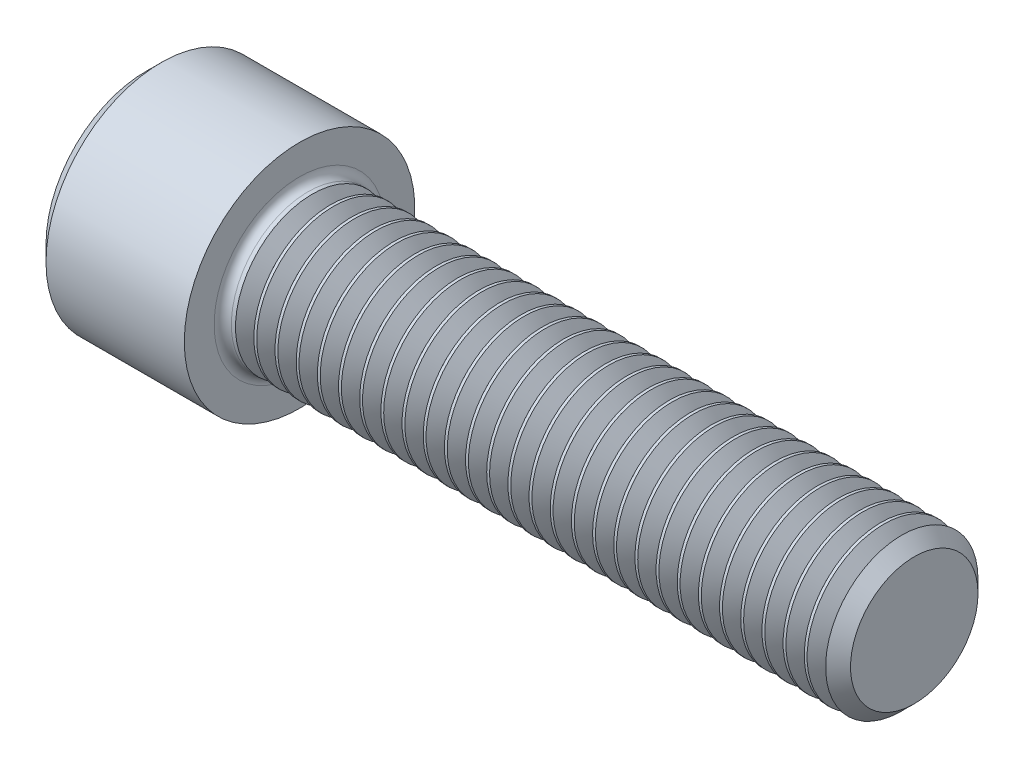
SolidWorks part; units mm, degrees
material "Chrome Stainless Steel"
ref_plane "Front Plane" through (0, 0, 0) normal (0, 0, 1) x (1, 0, 0)
ref_plane "Top Plane" through (0, 0, 0) normal (0, 1, 0) x (1, 0, 0)
ref_plane "Right Plane" through (0, 0, 0) normal (1, 0, 0) x (0, 0, -1)
ref_plane "Plane1" through (0, 0, 0) normal (0, 0, -1) x (-1, 0, 0)
sketch "Sketch1" plane through (0, 0, 0) normal (0, 0, -1) x (-1, 0, 0)
  line L0 (-6.35, 4.7625) -> (-6.35, 0)
  line L1 (-6.35, 0) -> (0, 0)
  line L2 (0, 0) -> (0, 4.7625)
  line L3 (0, 4.7625) -> (-6.35, 4.7625)
  line L4 (-6.35, 0) -> (0, 0) construction
revolve "Revolve1" add sketch "Sketch1" angle 360 about L4 reverse direction yes
sketch "Sketch2" plane through (6.35, 0, 0) normal (1, 0, 0) x (0, 0, -1)
  circle A0 centre (0, 0) radius 3.175
extrude "Boss-Extrude1" add sketch "Sketch2" along normal blind 0.528
sketch "Sketch3" plane through (6.878, 0, 0) normal (1, 0, 0) x (0, 0, -1)
  circle A0 centre (0, 0) radius 3.175
extrude "Boss-Extrude2" add sketch "Sketch3" along normal blind 0.3788 draft 55
sketch "Sketch4" plane through (7.2568, 0, 0) normal (1, 0, 0) x (0, 0, -1)
  circle A0 centre (0, 0) radius 2.634
extrude "Boss-Extrude3" add sketch "Sketch4" along normal blind 0.3788 draft 55 draft outward yes
sketch "Sketch5" plane through (7.6356, 0, 0) normal (1, 0, 0) x (0, 0, -1)
  circle A0 centre (0, 0) radius 3.175
extrude "Boss-Extrude4" add sketch "Sketch5" along normal blind 0.1171
sketch "Sketch6" plane through (7.7527, 0, 0) normal (1, 0, 0) x (0, 0, -1)
  circle A0 centre (0, 0) radius 3.175
extrude "Boss-Extrude5" add sketch "Sketch6" along normal blind 0.3788 draft 55
sketch "Sketch7" plane through (8.1315, 0, 0) normal (1, 0, 0) x (0, 0, -1)
  circle A0 centre (0, 0) radius 2.634
extrude "Boss-Extrude6" add sketch "Sketch7" along normal blind 0.3788 draft 55 draft outward yes
sketch "Sketch8" plane through (8.5104, 0, 0) normal (1, 0, 0) x (0, 0, -1)
  circle A0 centre (0, 0) radius 3.175
extrude "Boss-Extrude7" add sketch "Sketch8" along normal blind 0.1171
sketch "Sketch9" plane through (8.6275, 0, 0) normal (1, 0, 0) x (0, 0, -1)
  circle A0 centre (0, 0) radius 3.175
extrude "Boss-Extrude8" add sketch "Sketch9" along normal blind 0.3788 draft 55
sketch "Sketch10" plane through (9.0063, 0, 0) normal (1, 0, 0) x (0, 0, -1)
  circle A0 centre (0, 0) radius 2.634
extrude "Boss-Extrude9" add sketch "Sketch10" along normal blind 0.3788 draft 55 draft outward yes
sketch "Sketch11" plane through (9.3851, 0, 0) normal (1, 0, 0) x (0, 0, -1)
  circle A0 centre (0, 0) radius 3.175
extrude "Boss-Extrude10" add sketch "Sketch11" along normal blind 0.1171
sketch "Sketch12" plane through (9.5022, 0, 0) normal (1, 0, 0) x (0, 0, -1)
  circle A0 centre (0, 0) radius 3.175
extrude "Boss-Extrude11" add sketch "Sketch12" along normal blind 0.3788 draft 55
sketch "Sketch13" plane through (9.8811, 0, 0) normal (1, 0, 0) x (0, 0, -1)
  circle A0 centre (0, 0) radius 2.634
extrude "Boss-Extrude12" add sketch "Sketch13" along normal blind 0.3788 draft 55 draft outward yes
sketch "Sketch14" plane through (10.2599, 0, 0) normal (1, 0, 0) x (0, 0, -1)
  circle A0 centre (0, 0) radius 3.175
extrude "Boss-Extrude13" add sketch "Sketch14" along normal blind 0.1171
sketch "Sketch15" plane through (10.377, 0, 0) normal (1, 0, 0) x (0, 0, -1)
  circle A0 centre (0, 0) radius 3.175
extrude "Boss-Extrude14" add sketch "Sketch15" along normal blind 0.3788 draft 55
sketch "Sketch16" plane through (10.7558, 0, 0) normal (1, 0, 0) x (0, 0, -1)
  circle A0 centre (0, 0) radius 2.634
extrude "Boss-Extrude15" add sketch "Sketch16" along normal blind 0.3788 draft 55 draft outward yes
sketch "Sketch17" plane through (11.1346, 0, 0) normal (1, 0, 0) x (0, 0, -1)
  circle A0 centre (0, 0) radius 3.175
extrude "Boss-Extrude16" add sketch "Sketch17" along normal blind 0.1171
sketch "Sketch18" plane through (11.2517, 0, 0) normal (1, 0, 0) x (0, 0, -1)
  circle A0 centre (0, 0) radius 3.175
extrude "Boss-Extrude17" add sketch "Sketch18" along normal blind 0.3788 draft 55
sketch "Sketch19" plane through (11.6306, 0, 0) normal (1, 0, 0) x (0, 0, -1)
  circle A0 centre (0, 0) radius 2.634
extrude "Boss-Extrude18" add sketch "Sketch19" along normal blind 0.3788 draft 55 draft outward yes
sketch "Sketch20" plane through (12.0094, 0, 0) normal (1, 0, 0) x (0, 0, -1)
  circle A0 centre (0, 0) radius 3.175
extrude "Boss-Extrude19" add sketch "Sketch20" along normal blind 0.1171
sketch "Sketch21" plane through (12.1265, 0, 0) normal (1, 0, 0) x (0, 0, -1)
  circle A0 centre (0, 0) radius 3.175
extrude "Boss-Extrude20" add sketch "Sketch21" along normal blind 0.3788 draft 55
sketch "Sketch22" plane through (12.5053, 0, 0) normal (1, 0, 0) x (0, 0, -1)
  circle A0 centre (0, 0) radius 2.634
extrude "Boss-Extrude21" add sketch "Sketch22" along normal blind 0.3788 draft 55 draft outward yes
sketch "Sketch23" plane through (12.8842, 0, 0) normal (1, 0, 0) x (0, 0, -1)
  circle A0 centre (0, 0) radius 3.175
extrude "Boss-Extrude22" add sketch "Sketch23" along normal blind 0.1171
sketch "Sketch24" plane through (13.0013, 0, 0) normal (1, 0, 0) x (0, 0, -1)
  circle A0 centre (0, 0) radius 3.175
extrude "Boss-Extrude23" add sketch "Sketch24" along normal blind 0.3788 draft 55
sketch "Sketch25" plane through (13.3801, 0, 0) normal (1, 0, 0) x (0, 0, -1)
  circle A0 centre (0, 0) radius 2.634
extrude "Boss-Extrude24" add sketch "Sketch25" along normal blind 0.3788 draft 55 draft outward yes
sketch "Sketch26" plane through (13.7589, 0, 0) normal (1, 0, 0) x (0, 0, -1)
  circle A0 centre (0, 0) radius 3.175
extrude "Boss-Extrude25" add sketch "Sketch26" along normal blind 0.1171
sketch "Sketch27" plane through (13.876, 0, 0) normal (1, 0, 0) x (0, 0, -1)
  circle A0 centre (0, 0) radius 3.175
extrude "Boss-Extrude26" add sketch "Sketch27" along normal blind 0.3788 draft 55
sketch "Sketch28" plane through (14.2548, 0, 0) normal (1, 0, 0) x (0, 0, -1)
  circle A0 centre (0, 0) radius 2.634
extrude "Boss-Extrude27" add sketch "Sketch28" along normal blind 0.3788 draft 55 draft outward yes
sketch "Sketch29" plane through (14.6337, 0, 0) normal (1, 0, 0) x (0, 0, -1)
  circle A0 centre (0, 0) radius 3.175
extrude "Boss-Extrude28" add sketch "Sketch29" along normal blind 0.1171
sketch "Sketch30" plane through (14.7508, 0, 0) normal (1, 0, 0) x (0, 0, -1)
  circle A0 centre (0, 0) radius 3.175
extrude "Boss-Extrude29" add sketch "Sketch30" along normal blind 0.3788 draft 55
sketch "Sketch31" plane through (15.1296, 0, 0) normal (1, 0, 0) x (0, 0, -1)
  circle A0 centre (0, 0) radius 2.634
extrude "Boss-Extrude30" add sketch "Sketch31" along normal blind 0.3788 draft 55 draft outward yes
sketch "Sketch32" plane through (15.5084, 0, 0) normal (1, 0, 0) x (0, 0, -1)
  circle A0 centre (0, 0) radius 3.175
extrude "Boss-Extrude31" add sketch "Sketch32" along normal blind 0.1171
sketch "Sketch33" plane through (15.6255, 0, 0) normal (1, 0, 0) x (0, 0, -1)
  circle A0 centre (0, 0) radius 3.175
extrude "Boss-Extrude32" add sketch "Sketch33" along normal blind 0.3788 draft 55
sketch "Sketch34" plane through (16.0044, 0, 0) normal (1, 0, 0) x (0, 0, -1)
  circle A0 centre (0, 0) radius 2.634
extrude "Boss-Extrude33" add sketch "Sketch34" along normal blind 0.3788 draft 55 draft outward yes
sketch "Sketch35" plane through (16.3832, 0, 0) normal (1, 0, 0) x (0, 0, -1)
  circle A0 centre (0, 0) radius 3.175
extrude "Boss-Extrude34" add sketch "Sketch35" along normal blind 0.1171
sketch "Sketch36" plane through (16.5003, 0, 0) normal (1, 0, 0) x (0, 0, -1)
  circle A0 centre (0, 0) radius 3.175
extrude "Boss-Extrude35" add sketch "Sketch36" along normal blind 0.3788 draft 55
sketch "Sketch37" plane through (16.8791, 0, 0) normal (1, 0, 0) x (0, 0, -1)
  circle A0 centre (0, 0) radius 2.634
extrude "Boss-Extrude36" add sketch "Sketch37" along normal blind 0.3788 draft 55 draft outward yes
sketch "Sketch38" plane through (17.2579, 0, 0) normal (1, 0, 0) x (0, 0, -1)
  circle A0 centre (0, 0) radius 3.175
extrude "Boss-Extrude37" add sketch "Sketch38" along normal blind 0.1171
sketch "Sketch39" plane through (17.375, 0, 0) normal (1, 0, 0) x (0, 0, -1)
  circle A0 centre (0, 0) radius 3.175
extrude "Boss-Extrude38" add sketch "Sketch39" along normal blind 0.3788 draft 55
sketch "Sketch40" plane through (17.7539, 0, 0) normal (1, 0, 0) x (0, 0, -1)
  circle A0 centre (0, 0) radius 2.634
extrude "Boss-Extrude39" add sketch "Sketch40" along normal blind 0.3788 draft 55 draft outward yes
sketch "Sketch41" plane through (18.1327, 0, 0) normal (1, 0, 0) x (0, 0, -1)
  circle A0 centre (0, 0) radius 3.175
extrude "Boss-Extrude40" add sketch "Sketch41" along normal blind 0.1171
sketch "Sketch42" plane through (18.2498, 0, 0) normal (1, 0, 0) x (0, 0, -1)
  circle A0 centre (0, 0) radius 3.175
extrude "Boss-Extrude41" add sketch "Sketch42" along normal blind 0.3788 draft 55
sketch "Sketch43" plane through (18.6286, 0, 0) normal (1, 0, 0) x (0, 0, -1)
  circle A0 centre (0, 0) radius 2.634
extrude "Boss-Extrude42" add sketch "Sketch43" along normal blind 0.3788 draft 55 draft outward yes
sketch "Sketch44" plane through (19.0075, 0, 0) normal (1, 0, 0) x (0, 0, -1)
  circle A0 centre (0, 0) radius 3.175
extrude "Boss-Extrude43" add sketch "Sketch44" along normal blind 0.1171
sketch "Sketch45" plane through (19.1246, 0, 0) normal (1, 0, 0) x (0, 0, -1)
  circle A0 centre (0, 0) radius 3.175
extrude "Boss-Extrude44" add sketch "Sketch45" along normal blind 0.3788 draft 55
sketch "Sketch46" plane through (19.5034, 0, 0) normal (1, 0, 0) x (0, 0, -1)
  circle A0 centre (0, 0) radius 2.634
extrude "Boss-Extrude45" add sketch "Sketch46" along normal blind 0.3788 draft 55 draft outward yes
sketch "Sketch47" plane through (19.8822, 0, 0) normal (1, 0, 0) x (0, 0, -1)
  circle A0 centre (0, 0) radius 3.175
extrude "Boss-Extrude46" add sketch "Sketch47" along normal blind 0.1171
sketch "Sketch48" plane through (19.9993, 0, 0) normal (1, 0, 0) x (0, 0, -1)
  circle A0 centre (0, 0) radius 3.175
extrude "Boss-Extrude47" add sketch "Sketch48" along normal blind 0.3788 draft 55
sketch "Sketch49" plane through (20.3781, 0, 0) normal (1, 0, 0) x (0, 0, -1)
  circle A0 centre (0, 0) radius 2.634
extrude "Boss-Extrude48" add sketch "Sketch49" along normal blind 0.3788 draft 55 draft outward yes
sketch "Sketch50" plane through (20.757, 0, 0) normal (1, 0, 0) x (0, 0, -1)
  circle A0 centre (0, 0) radius 3.175
extrude "Boss-Extrude49" add sketch "Sketch50" along normal blind 0.1171
sketch "Sketch51" plane through (20.8741, 0, 0) normal (1, 0, 0) x (0, 0, -1)
  circle A0 centre (0, 0) radius 3.175
extrude "Boss-Extrude50" add sketch "Sketch51" along normal blind 0.3788 draft 55
sketch "Sketch52" plane through (21.2529, 0, 0) normal (1, 0, 0) x (0, 0, -1)
  circle A0 centre (0, 0) radius 2.634
extrude "Boss-Extrude51" add sketch "Sketch52" along normal blind 0.3788 draft 55 draft outward yes
sketch "Sketch53" plane through (21.6317, 0, 0) normal (1, 0, 0) x (0, 0, -1)
  circle A0 centre (0, 0) radius 3.175
extrude "Boss-Extrude52" add sketch "Sketch53" along normal blind 0.1171
sketch "Sketch54" plane through (21.7488, 0, 0) normal (1, 0, 0) x (0, 0, -1)
  circle A0 centre (0, 0) radius 3.175
extrude "Boss-Extrude53" add sketch "Sketch54" along normal blind 0.3788 draft 55
sketch "Sketch55" plane through (22.1277, 0, 0) normal (1, 0, 0) x (0, 0, -1)
  circle A0 centre (0, 0) radius 2.634
extrude "Boss-Extrude54" add sketch "Sketch55" along normal blind 0.3788 draft 55 draft outward yes
sketch "Sketch56" plane through (22.5065, 0, 0) normal (1, 0, 0) x (0, 0, -1)
  circle A0 centre (0, 0) radius 3.175
extrude "Boss-Extrude55" add sketch "Sketch56" along normal blind 0.1171
sketch "Sketch57" plane through (22.6236, 0, 0) normal (1, 0, 0) x (0, 0, -1)
  circle A0 centre (0, 0) radius 3.175
extrude "Boss-Extrude56" add sketch "Sketch57" along normal blind 0.3788 draft 55
sketch "Sketch58" plane through (23.0024, 0, 0) normal (1, 0, 0) x (0, 0, -1)
  circle A0 centre (0, 0) radius 2.634
extrude "Boss-Extrude57" add sketch "Sketch58" along normal blind 0.3788 draft 55 draft outward yes
sketch "Sketch59" plane through (23.3812, 0, 0) normal (1, 0, 0) x (0, 0, -1)
  circle A0 centre (0, 0) radius 3.175
extrude "Boss-Extrude58" add sketch "Sketch59" along normal blind 0.1171
sketch "Sketch60" plane through (23.4984, 0, 0) normal (1, 0, 0) x (0, 0, -1)
  circle A0 centre (0, 0) radius 3.175
extrude "Boss-Extrude59" add sketch "Sketch60" along normal blind 0.3788 draft 55
sketch "Sketch61" plane through (23.8772, 0, 0) normal (1, 0, 0) x (0, 0, -1)
  circle A0 centre (0, 0) radius 2.634
extrude "Boss-Extrude60" add sketch "Sketch61" along normal blind 0.3788 draft 55 draft outward yes
sketch "Sketch62" plane through (24.256, 0, 0) normal (1, 0, 0) x (0, 0, -1)
  circle A0 centre (0, 0) radius 3.175
extrude "Boss-Extrude61" add sketch "Sketch62" along normal blind 0.1171
sketch "Sketch63" plane through (24.3731, 0, 0) normal (1, 0, 0) x (0, 0, -1)
  circle A0 centre (0, 0) radius 3.175
extrude "Boss-Extrude62" add sketch "Sketch63" along normal blind 0.3788 draft 55
sketch "Sketch64" plane through (24.7519, 0, 0) normal (1, 0, 0) x (0, 0, -1)
  circle A0 centre (0, 0) radius 2.634
extrude "Boss-Extrude63" add sketch "Sketch64" along normal blind 0.3788 draft 55 draft outward yes
sketch "Sketch65" plane through (25.1308, 0, 0) normal (1, 0, 0) x (0, 0, -1)
  circle A0 centre (0, 0) radius 3.175
extrude "Boss-Extrude64" add sketch "Sketch65" along normal blind 0.1171
sketch "Sketch66" plane through (25.2479, 0, 0) normal (1, 0, 0) x (0, 0, -1)
  circle A0 centre (0, 0) radius 3.175
extrude "Boss-Extrude65" add sketch "Sketch66" along normal blind 0.3788 draft 55
sketch "Sketch67" plane through (25.6267, 0, 0) normal (1, 0, 0) x (0, 0, -1)
  circle A0 centre (0, 0) radius 2.634
extrude "Boss-Extrude66" add sketch "Sketch67" along normal blind 0.3788 draft 55 draft outward yes
sketch "Sketch68" plane through (26.0055, 0, 0) normal (1, 0, 0) x (0, 0, -1)
  circle A0 centre (0, 0) radius 3.175
extrude "Boss-Extrude67" add sketch "Sketch68" along normal blind 0.1171
sketch "Sketch69" plane through (26.1226, 0, 0) normal (1, 0, 0) x (0, 0, -1)
  circle A0 centre (0, 0) radius 3.175
extrude "Boss-Extrude68" add sketch "Sketch69" along normal blind 0.3788 draft 55
sketch "Sketch70" plane through (26.5015, 0, 0) normal (1, 0, 0) x (0, 0, -1)
  circle A0 centre (0, 0) radius 2.634
extrude "Boss-Extrude69" add sketch "Sketch70" along normal blind 0.3788 draft 55 draft outward yes
sketch "Sketch71" plane through (26.8803, 0, 0) normal (1, 0, 0) x (0, 0, -1)
  circle A0 centre (0, 0) radius 3.175
extrude "Boss-Extrude70" add sketch "Sketch71" along normal blind 0.1171
sketch "Sketch72" plane through (26.9974, 0, 0) normal (1, 0, 0) x (0, 0, -1)
  circle A0 centre (0, 0) radius 3.175
extrude "Boss-Extrude71" add sketch "Sketch72" along normal blind 0.3788 draft 55
sketch "Sketch73" plane through (27.3762, 0, 0) normal (1, 0, 0) x (0, 0, -1)
  circle A0 centre (0, 0) radius 2.634
extrude "Boss-Extrude72" add sketch "Sketch73" along normal blind 0.3788 draft 55 draft outward yes
sketch "Sketch74" plane through (27.755, 0, 0) normal (1, 0, 0) x (0, 0, -1)
  circle A0 centre (0, 0) radius 3.175
extrude "Boss-Extrude73" add sketch "Sketch74" along normal blind 0.1171
sketch "Sketch75" plane through (27.8721, 0, 0) normal (1, 0, 0) x (0, 0, -1)
  circle A0 centre (0, 0) radius 3.175
extrude "Boss-Extrude74" add sketch "Sketch75" along normal blind 0.3788 draft 55
sketch "Sketch76" plane through (28.251, 0, 0) normal (1, 0, 0) x (0, 0, -1)
  circle A0 centre (0, 0) radius 2.634
extrude "Boss-Extrude75" add sketch "Sketch76" along normal blind 0.3788 draft 55 draft outward yes
sketch "Sketch77" plane through (28.6298, 0, 0) normal (1, 0, 0) x (0, 0, -1)
  circle A0 centre (0, 0) radius 3.175
extrude "Boss-Extrude76" add sketch "Sketch77" along normal blind 0.1171
sketch "Sketch78" plane through (28.7469, 0, 0) normal (1, 0, 0) x (0, 0, -1)
  circle A0 centre (0, 0) radius 3.175
extrude "Boss-Extrude77" add sketch "Sketch78" along normal blind 0.3788 draft 55
sketch "Sketch79" plane through (29.1257, 0, 0) normal (1, 0, 0) x (0, 0, -1)
  circle A0 centre (0, 0) radius 2.634
extrude "Boss-Extrude78" add sketch "Sketch79" along normal blind 0.3788 draft 55 draft outward yes
sketch "Sketch80" plane through (29.5046, 0, 0) normal (1, 0, 0) x (0, 0, -1)
  circle A0 centre (0, 0) radius 3.175
extrude "Boss-Extrude79" add sketch "Sketch80" along normal blind 0.1171
sketch "Sketch81" plane through (29.6217, 0, 0) normal (1, 0, 0) x (0, 0, -1)
  circle A0 centre (0, 0) radius 3.175
extrude "Boss-Extrude80" add sketch "Sketch81" along normal blind 0.3788 draft 55
sketch "Sketch82" plane through (30.0005, 0, 0) normal (1, 0, 0) x (0, 0, -1)
  circle A0 centre (0, 0) radius 2.634
extrude "Boss-Extrude81" add sketch "Sketch82" along normal blind 0.3788 draft 55 draft outward yes
sketch "Sketch83" plane through (30.3793, 0, 0) normal (1, 0, 0) x (0, 0, -1)
  circle A0 centre (0, 0) radius 3.175
extrude "Boss-Extrude82" add sketch "Sketch83" along normal blind 0.1171
sketch "Sketch84" plane through (30.4964, 0, 0) normal (1, 0, 0) x (0, 0, -1)
  circle A0 centre (0, 0) radius 3.175
extrude "Boss-Extrude83" add sketch "Sketch84" along normal blind 0.3788 draft 55
sketch "Sketch85" plane through (30.8752, 0, 0) normal (1, 0, 0) x (0, 0, -1)
  circle A0 centre (0, 0) radius 2.634
extrude "Boss-Extrude84" add sketch "Sketch85" along normal blind 0.3603 draft 55 draft outward yes
sketch "Sketch86" plane through (31.2355, 0, 0) normal (1, 0, 0) x (0, 0, -1)
  circle A0 centre (0, 0) radius 3.1485
extrude "Boss-Extrude85" add sketch "Sketch86" along normal blind 0.5145 draft 45
sketch "Sketch87" plane through (0, 0, 0) normal (-1, 0, 0) x (0, 0, 1)
  line L0 (-2.3812, -1.3748) -> (0, -2.7496)
  line L1 (0, -2.7496) -> (2.3812, -1.3748)
  line L2 (2.3812, -1.3748) -> (2.3812, 1.3748)
  line L3 (2.3812, 1.3748) -> (0, 2.7496)
  line L4 (0, 2.7496) -> (-2.3813, 1.3748)
  line L5 (-2.3813, 1.3748) -> (-2.3812, -1.3748)
extrude "Cut-Extrude1" cut sketch "Sketch87" against normal blind 3.048
sketch "Sketch88" plane through (0, 0, 0) normal (0, 0, 1) x (1, 0, 0)
  line L0 (3.048, 2.3813) -> (3.048, 0)
  line L1 (3.048, 0) -> (4.4228, 0)
  line L2 (4.4228, 0) -> (3.048, 2.3813)
  line L3 (3.048, 0) -> (4.4229, 0) construction
revolve "Cut-Revolve1" cut sketch "Sketch88" angle 360 about L3 reverse direction yes
chamfer "Chamfer1" distance 0.635 angle 45 1 edges at (0, 0, 4.7625)
fillet "Fillet1" radius 0.3556 1 edges at (6.35, 0, -3.175) tangent propagation no
